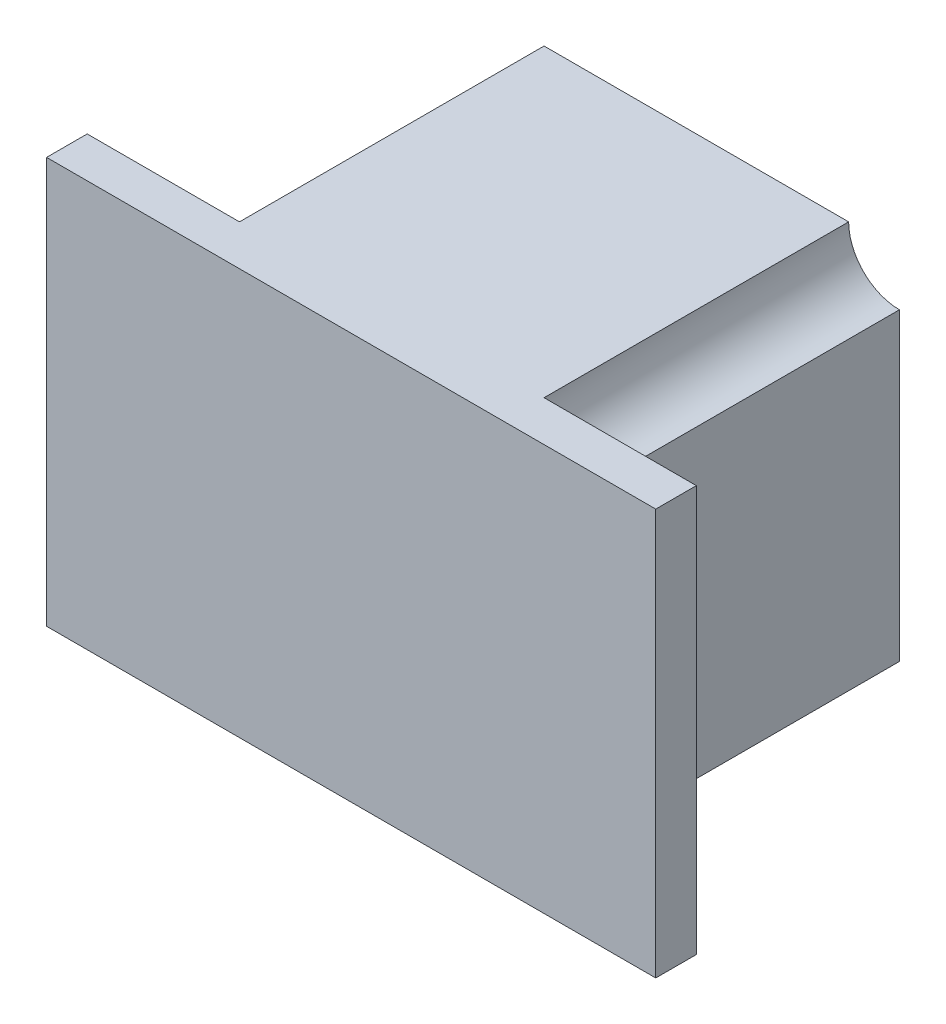
SolidWorks part; units mm, degrees
ref_plane "Front Plane" through (0, 0, 0) normal (0, 0, 1) x (1, 0, 0)
ref_plane "Top Plane" through (0, 0, 0) normal (0, 1, 0) x (1, 0, 0)
ref_plane "Right Plane" through (0, 0, 0) normal (1, 0, 0) x (0, 0, -1)
sketch "Sketch1" plane through (0, 0, 0) normal (0, 0, 1) x (1, 0, 0)
  line L1 (-150, -100) -> (150, -100)
  line L2 (-150, -100) -> (-150, 100)
  line L3 (-150, 100) -> (150, 100)
  line L4 (150, -100) -> (150, 100)
  line L5 (-150, -100) -> (150, 100) construction
  line L6 (-150, 100) -> (150, -100) construction
  point P0 (0, 0)
  dimension "D1" = 300
  dimension "D2" = 200
extrude "Boss-Extrude1" add sketch "Sketch1" along normal blind 20
sketch "Sketch2" plane through (0, 0, 0) normal (0, 0, -1) x (-1, 0, 0)
  line L0 (-150, 100) -> (150, 100) construction
  line L1 (-75, -100) -> (75, -100)
  line L2 (-75, -100) -> (-75, 100)
  line L3 (-75, 100) -> (75, 100)
  line L4 (75, -100) -> (75, 100)
  line L5 (-75, -100) -> (75, 100) construction
  line L6 (-75, 100) -> (75, -100) construction
  line L8 (-100, -75) -> (100, -75)
  line L9 (-100, -75) -> (-100, 75)
  line L10 (-100, 75) -> (100, 75)
  line L11 (100, -75) -> (100, 75)
  line L12 (-100, -75) -> (100, 75) construction
  line L13 (-100, 75) -> (100, -75) construction
  point P0 (0, 0)
  point P8 (0, 0)
  line M10 (-150, -100) -> (150, -100)
  line M12 (150, 100) -> (-150, 100)
  dimension "D1" = 150
  dimension "D2" = 150
  dimension "D3" = 200
extrude "Boss-Extrude2" add sketch "Sketch2" along normal blind 150 contours L2 L10 L4 M12 | L10 L2 L8 L4 | L10 L9 L8 L2 | L8 L11 L10 L4 | L8 L2 L4 M10 region at (0, -87.5, 0) region at (87.5, 0, 0) region at (0, 0, 0) region at (-87.5, 0, 0) region at (0, 87.5, 0)
fillet "Fillet1" radius 25 1 edges at (75, 75, -75)
fillet "Fillet2" radius 25 3 edges at (75, -75, -75) (-75, -75, -75) (-75, 75, -75)
